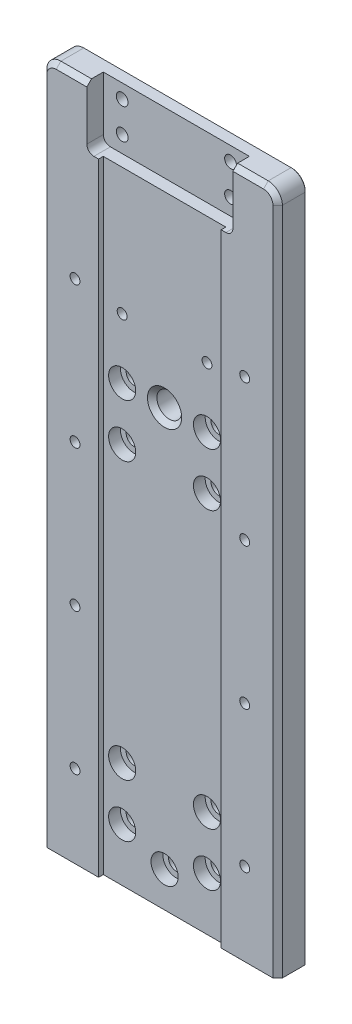
SolidWorks part; units mm, degrees
material "1060 Alloy"
ref_plane "Front Plane" through (0, 0, 0) normal (0, 0, 1) x (1, 0, 0)
ref_plane "Top Plane" through (0, 0, 0) normal (0, 1, 0) x (1, 0, 0)
ref_plane "Right Plane" through (0, 0, 0) normal (1, 0, 0) x (0, 0, -1)
sketch "Sketch1" plane through (0, 0, 0) normal (0, 0, 1) x (1, 0, 0)
  line L1 (50, -145) -> (-50, -145)
  line L2 (50, -145) -> (50, 145)
  line L3 (50, 145) -> (-50, 145)
  line L4 (-50, -145) -> (-50, 145)
  line L5 (50, -145) -> (-50, 145) construction
  line L6 (50, 145) -> (-50, -145) construction
  point P0 (0, 0)
  dimension "D1" = 100
  dimension "D2" = 290
extrude "Boss-Extrude1" add sketch "Sketch1" along normal mid plane 12
sketch "Sketch2" plane through (0, 0, 6) normal (0, 0, 1) x (1, 0, 0)
  line L0 (0, 132) -> (0, 0) construction
  line L1 (31, 119) -> (-31, 119)
  line L2 (31, 119) -> (31, 145)
  line L3 (31, 145) -> (-31, 145)
  line L4 (-31, 119) -> (-31, 145)
  line L5 (31, 119) -> (-31, 145) construction
  line L6 (31, 145) -> (-31, 119) construction
  line L7 (50, 145) -> (-50, 145) construction
  point P0 (0, 132)
  dimension "D1" = 62
  dimension "D2" = 26
extrude "Cut-Extrude1" cut sketch "Sketch2" against normal blind 7
sketch "Sketch3" plane through (0, 0, 6) normal (0, 0, 1) x (1, 0, 0)
  line L0 (-50, -145) -> (50, -145) construction
  line L1 (26, 145) -> (-26, 145)
  line L2 (26, 145) -> (26, -145)
  line L3 (26, -145) -> (-26, -145)
  line L4 (-26, 145) -> (-26, -145)
  line L5 (26, 145) -> (-26, -145) construction
  line L6 (26, -145) -> (-26, 145) construction
  point P0 (0, 0)
  dimension "D1" = 52
extrude "Cut-Extrude2" cut sketch "Sketch3" against normal blind 2
sketch "Sketch4" plane through (0, 0, -6) normal (0, 0, 1) x (1, 0, 0)
  line L0 (0, 132.5) -> (0, 0) construction
  line L1 (23, 126) -> (-23, 126) construction
  line L2 (23, 126) -> (23, 139) construction
  line L3 (23, 139) -> (-23, 139) construction
  line L4 (-23, 126) -> (-23, 139) construction
  line L5 (23, 126) -> (-23, 139) construction
  line L6 (23, 139) -> (-23, 126) construction
  line L7 (31, 145) -> (-31, 145) construction
  line L8 (-18, 65.14) -> (-18, 17.14) construction
  line L9 (-36, 145) -> (-36, -110) construction
  line L10 (-31, 145) -> (-50, 145) construction
  line L11 (-50, -145) -> (-26, -145) construction
  line L12 (0, 0) -> (0, -145) construction
  line L13 (-26, -145) -> (26, -145) construction
  line L14 (50, 5.14) -> (-50, 5.14) construction
  line L15 (18, -100) -> (-18, -100) construction
  line L16 (18, -100) -> (18, -122.5) construction
  line L17 (18, -122.5) -> (-18, -122.5) construction
  line L18 (-18, -100) -> (-18, -122.5) construction
  line L19 (18, -100) -> (-18, -122.5) construction
  line L20 (18, -122.5) -> (-18, -100) construction
  line L21 (50, 5.14) -> (50, 55.14) construction
  line L22 (50, 55.14) -> (-50, 55.14) construction
  line L23 (-50, 5.14) -> (-50, 55.14) construction
  line L24 (50, 5.14) -> (-50, 55.14) construction
  line L25 (50, 55.14) -> (-50, 5.14) construction
  circle A0 centre (-23, 139) radius 2.5
  circle A1 centre (23, 139) radius 2.5
  circle A2 centre (23, 126) radius 2.5
  circle A3 centre (-23, 126) radius 2.5
  circle A4 centre (0, 39.64) radius 5.25
  circle A5 centre (-18, 65.14) radius 2.1
  circle A6 centre (-18, 39.64) radius 3.3
  circle A7 centre (-18, 17.14) radius 3.3
  circle A9 centre (-36, 70) radius 2.1
  circle A10 centre (-36, 58.75) radius 2.1 construction
  circle A11 centre (-36, 10) radius 2.1
  circle A12 centre (-36, -110) radius 2.1
  circle A13 centre (-36, -50) radius 2.1
  circle A14 centre (-18, -100) radius 3.3
  circle A15 centre (-18, -122.5) radius 3.3
  circle A16 centre (18, -100) radius 3.3
  circle A17 centre (18, -122.5) radius 3.3
  circle A18 centre (0, -130) radius 3.3
  circle A20 centre (36, 70) radius 2.1
  circle A21 centre (36, 58.75) radius 2.1 construction
  circle A22 centre (18, 65.14) radius 2.1
  circle A23 centre (18, 17.14) radius 3.3
  circle A24 centre (18, 39.64) radius 3.3
  circle A25 centre (36, 10) radius 2.1
  circle A26 centre (36, -50) radius 2.1
  circle A27 centre (36, -110) radius 2.1
  point P0 (0, 132.5)
  point P36 (0, -111.25)
  point P68 (0, 30.14)
  dimension "D1" = 5
  dimension "D5" = 10.5
  dimension "D12" = 4.2
  dimension "D19" = 6.6
  dimension "D9" = 6.6
  dimension "D2" = 13
  dimension "D3" = 46
  dimension "D4" = 6
  dimension "D8" = 18
  dimension "D10" = 22.5
  dimension "D11" = 36
  dimension "D13" = 35
  dimension "D14" = 60
  dimension "D15" = 60
  dimension "D16" = 48.75
  dimension "D17" = 11.25
  dimension "D20" = 15
  dimension "D21" = 36
  dimension "D23" = 22.5
  dimension "D24" = 100
  dimension "D25" = 50
  dimension "D7" = 10
  dimension "D6" = 12
  dimension "D18" = 150.14
  dimension "D22" = 7.5
extrude "Cut-Extrude HOLES" cut sketch "Sketch4" along normal blind 21
fillet "Fillet1" radius 3 2 edges at (31, 119, 2.5) (-31, 119, 2.5)
fillet "Fillet2" radius 6 2 edges at (50, 145, 0) (-50, 145, 0)
chamfer "Chamfer1" distance 2 angle 45 6 edges at (50, -3, 6) (48.2426, 143.2426, 6) (37.5, 145, 6) (-50, -3, 6) (-48.2426, 143.2426, 6) (-37.5, 145, 6)
sketch "Sketch5" plane through (0, 0, 4) normal (0, 0, 1) x (1, 0, 0)
  circle A1 centre (-18, 39.64) radius 5.75
  circle A2 centre (-18, 17.14) radius 5.75
  circle A3 centre (18, 17.14) radius 5.75
  circle A4 centre (18, 39.64) radius 5.75
  circle A6 centre (18, -100) radius 5.75
  circle A7 centre (-18, -100) radius 5.75
  circle A8 centre (-18, -122.5) radius 5.75
  circle A9 centre (0, -130) radius 5.75
  circle A10 centre (18, -122.5) radius 5.75
  dimension "D1" = 11.5
extrude "Cut-Extrude5" cut sketch "Sketch5" against normal blind 5
chamfer "Chamfer2" distance 2 angle 45 1 edges at (-5.25, 39.64, 4)
chamfer "Chamfer3" distance 0.3 angle 45 5 edges at (-50, -3, -6) (-48.2426, 143.2426, -6) (48.2426, 143.2426, -6) (50, -3, -6) (0, 145, -6)
equation "\"M5_tap\"=4.2mm"
equation "\"M5_clearence\"=5.5mm"
equation "\"M6_tap\"=5mm"
equation "\"M6_clearence\"=6.6mm"
equation "\"D1@Sketch4\"=\"M6_tap\""
equation "\"D12@Sketch4\"=\"M5_tap\""
equation "\"D19@Sketch4\"=\"M6_clearence\""
equation "\"work_area_width\"=1100mm"
equation "\"work_area_depth\"=900mm"
equation "\"steel_base_width\"=80mm"
equation "\"steel_base_height\"=50mm"
equation "\"steel_base_wall_thickness\"=3mm"
equation "\"steel_base_radius\"=6mm"
equation "\"steel_sides_width\"=80mm"
equation "\"steel_sides_height\"=50mm"
equation "\"steel_sides_wall_thickness\"=5mm"
equation "\"steel_sides_radius\"=6mm"
equation "\"steel_gantry_width\"=80mm"
equation "\"steel_gantry_height\"=50mm"
equation "\"steel_gantry_wall_thickness\"=6mm"
equation "\"steel_gantry_radius\"=6mm"
equation "\"steel_rollers_width\"=80mm"
equation "\"steel_rollers_height\"=50mm"
equation "\"steel_rollers_wall_thickness\"=6mm"
equation "\"steel_rollers_radius\"=6mm"
equation "\"steel_zbox_width\"=80mm"
equation "\"steel_zbox_height\"=50mm"
equation "\"steel_zbox_wall_thickness\"=3mm"
equation "\"steel_zbox_radius\"=6mm"
equation "\"alu_zangle_width\"=80mm"
equation "\"alu_zangle_height\"=50mm"
equation "\"alu_zangle_wall_thickness\"=10mm"
equation "\"D9@Sketch4\"=\"M6_clearence\""
equation "\"D25@Sketch4\"=\"steel_zbox_height\""
equation "\"D6@Sketch4\"=\"steel_zbox_radius\"*2"
equation "\"D18@Sketch4\"=\"steel_gantry_width\" + \"alu_zangle_wall_thickness\" + 60.14"
equation "\"D20@Sketch4\"=\"alu_zangle_wall_thickness\" + 5"
